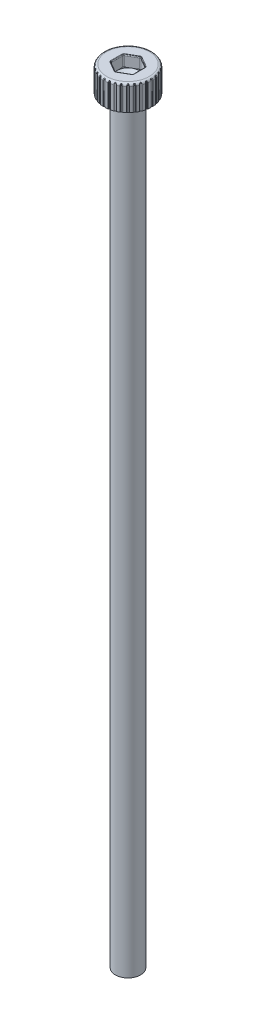
SolidWorks part; units mm, degrees
material "1060 Alloy"
ref_plane "Front Plane" through (0, 0, 0) normal (0, 0, 1) x (1, 0, 0)
ref_plane "Top Plane" through (0, 0, 0) normal (0, 1, 0) x (1, 0, 0)
ref_plane "Right Plane" through (0, 0, 0) normal (1, 0, 0) x (0, 0, -1)
sketch "Sketch1" plane through (0, 0, 0) normal (0, 1, 0) x (1, 0, 0)
  line L1 (0, 1.4896) -> (-1.29, 0.7448) construction
  line L2 (-1.29, 0.7448) -> (-1.29, -0.7448) construction
  line L3 (-1.29, -0.7448) -> (0, -1.4896) construction
  line L4 (0, -1.4896) -> (1.29, -0.7448) construction
  line L5 (1.29, -0.7448) -> (1.29, 0.7448) construction
  line L6 (1.29, 0.7448) -> (0, 1.4896) construction
  circle A0 centre (0, 0) radius 2.84
  circle A1 centre (0, 0) radius 1.29 construction
  dimension "dk" = 5.68
  dimension "s" = 2.58
extrude "Boss-Extrude1" add sketch "Sketch1" along normal blind 3
sketch "Sketch2" plane through (0, 0, 0) normal (0, -1, 0) x (1, 0, 0)
  circle A0 centre (0, 0) radius 1.5
  dimension "dia" = 3
extrude "Boss-Extrude2" add sketch "Sketch2" along normal blind 90
sketch "Sketch3" plane through (0, 3, 0) normal (0, 1, 0) x (1, 0, 0)
  line L0 (1.29, 0.7448) -> (0, 1.4896) construction
  line L1 (1.29, -0.7448) -> (1.29, 0.7448) construction
  line L2 (0, -1.4896) -> (1.29, -0.7448) construction
  line L3 (-1.29, -0.7448) -> (0, -1.4896) construction
  line L4 (-1.29, 0.7448) -> (-1.29, -0.7448) construction
  line L5 (0, 1.4896) -> (-1.29, 0.7448) construction
  line L6 (1.29, 0.7448) -> (0, 1.4896)
  line L7 (1.29, -0.7448) -> (1.29, 0.7448)
  line L8 (0, -1.4896) -> (1.29, -0.7448)
  line L9 (-1.29, -0.7448) -> (0, -1.4896)
  line L10 (-1.29, 0.7448) -> (-1.29, -0.7448)
  line L11 (0, 1.4896) -> (-1.29, 0.7448)
extrude "Cut-Extrude1" cut sketch "Sketch3" against normal blind 1.3
sketch "Sketch4" plane through (0, 0, 0) normal (0, 0, 1) x (1, 0, 0)
  line L0 (0, 1.7) -> (0, 0.9552)
  line L1 (0, 0.9552) -> (1.29, 1.7)
  line L2 (1.29, 1.7) -> (1.29, 3) construction
  line L3 (1.29, 1.7) -> (0, 1.7)
  line L4 (0, 0.9552) -> (0, 0) construction
  line L5 (2.84, 0) -> (-2.84, 0) construction
  dimension "D1" = 60
revolve "Cut-Revolve1" cut sketch "Sketch4" angle 360 about L4
fillet "Fillet1" radius 0.3 1 edges at (0, 3, 2.84)
sketch "Sketch5" plane through (0, 0, 0) normal (0, -1, 0) x (1, 0, 0)
  line L0 (0, 0) -> (0, 2.84) construction
  circle A0 centre (0, 0) radius 2.84 construction
  circle A1 centre (0, 2.84) radius 0.075
  dimension "D1" = 0.15
extrude "Cut-Extrude2" cut sketch "Sketch5" against normal through all
fillet "Fillet2" radius 0.075 3 edges at (0.075, 1.35, 2.839) (0.0002, 2.8984, 2.765) (-0.075, 1.35, 2.839)
pattern_circular "CirPattern1" count 32 over 360 about axis through (0, 3, 0) along (0, -1, 0) of "Cut-Extrude2", "Fillet2"
chamfer "Chamfer1" distance 0.075 angle 45 6 edges at (0.645, 3, -1.1172) (1.29, 3, 0) (0.645, 3, 1.1172) (-0.645, 3, 1.1172) (-1.29, 3, 0) (-0.645, 3, -1.1172)
fillet "Fillet3" radius 0.15 6 edges at (-0.645, 2.925, -1.1172) (0.645, 2.925, -1.1172) (1.29, 2.925, 0) (-1.29, 2.925, 0) (-0.645, 2.925, 1.1172) (0.645, 2.925, 1.1172)
fillet "Fillet4" radius 0.15 18 edges at (1.29, 2.2814, -0.7448) (1.3495, 2.9845, -0.7791) (0, 2.2814, -1.4896) (0, 2.9845, -1.5582) (-1.3495, 2.9845, -0.7791) (-1.29, 2.2814, -0.7448) (-1.3495, 2.9845, 0.7791) (-1.29, 2.2814, 0.7448) (0, 2.9845, 1.5582) (0, 2.2814, 1.4896) (1.29, 2.2814, 0.7448) (1.3495, 2.9845, 0.7791) (1.3014, 2.9203, -0.7514) (0, 2.9203, -1.5027) (-1.3014, 2.9203, -0.7514) (-1.3014, 2.9203, 0.7514) (0, 2.9203, 1.5027) (1.3014, 2.9203, 0.7514)
fillet "Fillet5" radius 0.075 12 edges at (-1.3513, 3, 0.7802) (-0.6825, 3, 1.1821) (0, 3, 1.5603) (0.6825, 3, 1.1821) (1.3513, 3, 0.7802) (1.365, 3, 0) (1.3513, 3, -0.7802) (0.6825, 3, -1.1821) (0, 3, -1.5603) (-0.6825, 3, -1.1821) (-1.3513, 3, -0.7802) (-1.365, 3, 0)
equation "\"D1@Fillet1\"=\"dia@Sketch2\"/10"
equation "\"D1@Sketch5\"=\"D1@Fillet1\"/2"
equation "\"D1@Fillet2\"=\"D1@Sketch5\"/2"
equation "\"D1@Chamfer1\"=\"D1@Fillet2\""
equation "\"D1@Fillet3\"=\"D1@Sketch5\""
equation "\"D1@Fillet4\"=\"D1@Fillet3\""
equation "\"D1@Fillet5\"=\"D1@Chamfer1\""
